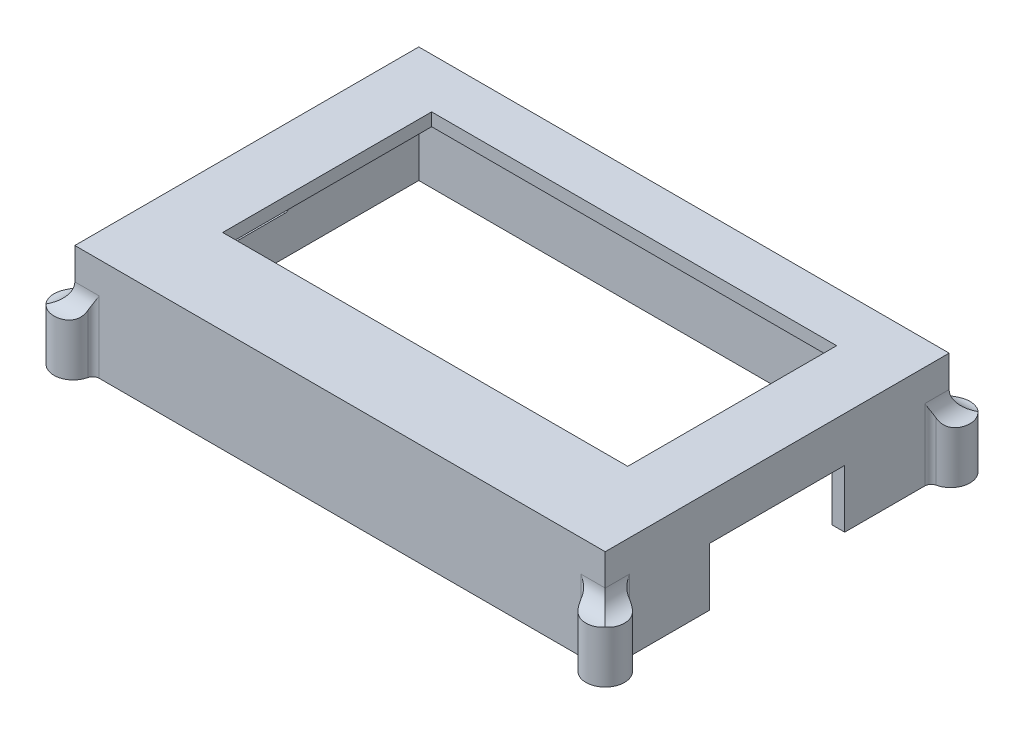
SolidWorks part; units mm, degrees
ref_plane "前视基准面" through (0, 0, 0) normal (0, 0, 1) x (1, 0, 0)
ref_plane "上视基准面" through (0, 0, 0) normal (0, 1, 0) x (1, 0, 0)
ref_plane "右视基准面" through (0, 0, 0) normal (1, 0, 0) x (0, 0, -1)
sketch "草图1" plane through (0, 0, 0) normal (0, 1, 0) x (1, 0, 0)
  line L1 (-39, 24.5) -> (39, 24.5)
  line L2 (-39, 24.5) -> (-39, -24.5)
  line L3 (-39, -24.5) -> (39, -24.5)
  line L4 (39, 24.5) -> (39, -24.5)
  line L5 (-39, 24.5) -> (39, -24.5) construction
  line L6 (-39, -24.5) -> (39, 24.5) construction
  point P0 (0, 0)
  dimension "D1" = 78
  dimension "D2" = 49
sketch "草图2" plane through (0, 0, 0) normal (0, 1, 0) x (1, 0, 0)
  line L0 (-39, -24.5) -> (39, -24.5) construction
  line L1 (-39.25, 24.75) -> (39.25, 24.75)
  line L2 (-39.25, 24.75) -> (-39.25, -24.75)
  line L3 (-39.25, -24.75) -> (39.25, -24.75)
  line L4 (39.25, 24.75) -> (39.25, -24.75)
  line L5 (-39.25, 24.75) -> (39.25, -24.75) construction
  line L6 (-39.25, -24.75) -> (39.25, 24.75) construction
  line L7 (39, 24.5) -> (39, -24.5) construction
  line L9 (-41.25, 26.75) -> (41.25, 26.75)
  line L10 (-41.25, 26.75) -> (-41.25, -26.75)
  line L11 (-41.25, -26.75) -> (41.25, -26.75)
  line L12 (41.25, 26.75) -> (41.25, -26.75)
  line L13 (-41.25, 26.75) -> (41.25, -26.75) construction
  line L14 (-41.25, -26.75) -> (41.25, 26.75) construction
  point P0 (0, 0)
  point P10 (0, 0)
  dimension "D1" = 0.25
  dimension "D2" = 0.25
  dimension "D3" = 2
  dimension "D4" = 2
extrude "凸台-拉伸1" add sketch "草图2" against normal blind 14
sketch "草图3" plane through (0, 0, 0) normal (0, 1, 0) x (1, 0, 0)
  line L0 (41.25, -26.75) -> (41.25, 26.75) construction
  line L1 (41.25, 26.75) -> (-41.25, 26.75) construction
  line L2 (-41.25, 26.75) -> (-41.25, -26.75) construction
  line L3 (-41.25, -26.75) -> (41.25, -26.75) construction
  line L4 (41.25, -26.75) -> (41.25, 26.75)
  line L5 (41.25, 26.75) -> (-41.25, 26.75)
  line L6 (-41.25, 26.75) -> (-41.25, -26.75)
  line L7 (-41.25, -26.75) -> (41.25, -26.75)
  line L8 (-31.5, 2.75) -> (-39, 2.75) construction
  line L9 (-31.5, 19) -> (31.5, 19)
  line L10 (-31.5, 19) -> (-31.5, -13.5)
  line L11 (-31.5, -13.5) -> (31.5, -13.5)
  line L12 (31.5, 19) -> (31.5, -13.5)
  line L13 (-31.5, 19) -> (31.5, -13.5) construction
  line L14 (-31.5, -13.5) -> (31.5, 19) construction
  line L15 (-39, 24.5) -> (-39, -24.5) construction
  line L16 (31.5, 2.75) -> (39, 2.75) construction
  line L17 (39, 24.5) -> (39, -24.5) construction
  line L18 (-39, 24.5) -> (39, 24.5) construction
  line L19 (-39, -24.5) -> (39, -24.5) construction
  point P2 (0, 2.75)
  dimension "D1" = 63
  dimension "D2" = 5.5
  dimension "D3" = 11
extrude "凸台-拉伸2" add sketch "草图3" along normal blind 2
sketch "草图4" plane through (0, 0, 0) normal (1, 0, 0) x (0, 0, -1)
  line L0 (0, -6.5) -> (0, 0) construction
  line L1 (4.5, -5) -> (-4.5, -5)
  line L2 (4.5, -5) -> (4.5, -8)
  line L3 (4.5, -8) -> (-4.5, -8)
  line L4 (-4.5, -5) -> (-4.5, -8)
  line L5 (4.5, -5) -> (-4.5, -8) construction
  line L6 (4.5, -8) -> (-4.5, -5) construction
  point P0 (0, -6.5)
  dimension "D1" = 6.5
  dimension "D2" = 9
  dimension "D3" = 3
extrude "切除-拉伸1" cut sketch "草图4" against normal through all
fillet "圆角1" radius 0.5 4 edges at (-40.25, -5, 4.5) (-40.25, -8, 4.5) (-40.25, -8, -4.5) (-40.25, -5, -4.5)
sketch "草图6" plane through (0, 0, 0) normal (1, 0, 0) x (0, 0, -1)
  line L0 (-26.75, -14) -> (26.75, -14) construction
  line L1 (-10.5, -14) -> (10.5, -14)
  line L2 (-10.5, -14) -> (-10.5, -5)
  line L3 (-10.5, -5) -> (10.5, -5)
  line L4 (10.5, -14) -> (10.5, -5)
  line L5 (0, -5) -> (0, 0) construction
  dimension "D1" = 5
  dimension "D2" = 21
extrude "切除-拉伸2" cut sketch "草图6" along normal through all
sketch "草图7" plane through (0, 0, 0) normal (0, 1, 0) x (1, 0, 0)
  line L6 (-41.25, -26.75) -> (-41.3713, -26.8713) construction
  line L7 (-41.25, -26.75) -> (41.25, -26.75) construction
  line L8 (0, -26.75) -> (0, 26.75) construction
  line L9 (41.25, 26.75) -> (-41.25, 26.75) construction
  line L10 (-41.25, 0) -> (41.25, 0) construction
  line L11 (-41.25, 26.75) -> (-41.25, -26.75) construction
  line L12 (41.25, 10.5) -> (41.25, -10.5) construction
  circle A1 centre (-41.3713, -26.8713) radius 3
  circle A2 centre (41.3713, -26.8713) radius 3
  circle A3 centre (-41.3713, 26.8713) radius 3
  circle A4 centre (41.3713, 26.8713) radius 3
  dimension "D1" = 135
  dimension "D2" = 6
extrude "凸台-拉伸3" add sketch "草图7" along normal blind 8 from surface starting at face at (13.4167, -14, 0)
sketch "草图8" plane through (0, 0, 0) normal (0, 1, 0) x (1, 0, 0)
  circle A0 centre (-41.3713, -26.8713) radius 0.85
  circle A1 centre (-41.3713, 26.8713) radius 0.85
  circle A2 centre (41.3713, 26.8713) radius 0.85
  circle A3 centre (41.3713, -26.8713) radius 0.85
  dimension "D1" = 1.7
extrude "切除-拉伸3" cut sketch "草图8" along normal blind 6 from surface starting at face at (10.0625, -14, 0)
fillet "圆角2" radius 1 8 edges at (38.3738, -10, 26.75) (41.25, -10, 23.8738) (41.25, -10, -23.8738) (38.3738, -10, -26.75) (-38.3738, -10, -26.75) (-41.25, -10, -23.8738) (-41.25, -10, 23.8738) (-38.3738, -10, 26.75)
fillet "圆角3" radius 3.1 8 edges at (-39.3595, -6, 26.75) (-41.25, -6, 24.8595) (-41.25, -6, -24.8595) (-39.3595, -6, -26.75) (39.3595, -6, -26.75) (41.25, -6, -24.8595) (41.25, -6, 24.8595) (39.3595, -6, 26.75)
